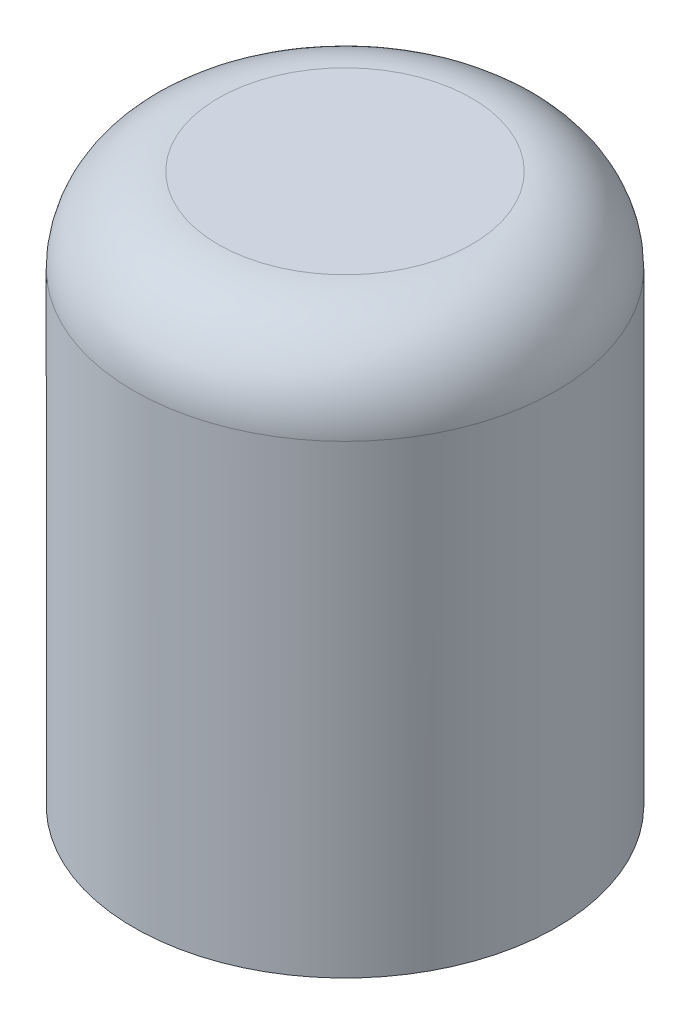
SolidWorks part; units mm, degrees
ref_plane "Front Plane" through (0, 0, 0) normal (0, 0, 1) x (1, 0, 0)
ref_plane "Top Plane" through (0, 0, 0) normal (0, 1, 0) x (1, 0, 0)
ref_plane "Right Plane" through (0, 0, 0) normal (1, 0, 0) x (0, 0, -1)
sketch "Sketch1" plane through (0, 0, 0) normal (0, 1, 0) x (1, 0, 0)
  circle A0 centre (0, 0) radius 5
  dimension "D1" = 10
extrude "Boss-Extrude1" add sketch "Sketch1" along normal blind 13
sketch "Insert" plane through (0, 0, 0) normal (0, -1, 0) x (1, 0, 0)
  line L0 (-1.6, 3) -> (-1.6, -3)
  line L1 (3.4, 0) -> (1.7771, 0) construction
  line L2 (-1.6, 0) -> (-0.8194, 0) construction
  arc A0 (-1.6, -3) -> (-1.6, 3) centre (0, 0) ccw
  dimension "D1" = 6
  dimension "D2" = 5
extrude "Cut-Extrude1" cut sketch "Insert" against normal blind 12.5
fillet "Fillet4" radius 2 2 edges at (3.4, 12.5, 0) (-1.6, 12.5, 0) type face fillet first side face at (-1.6, 6.25, 0) first side face at (0.9, 6.25, 0) second side face at (0.9, 12.5, 0)
fillet "Fillet5" radius 0.5 2 edges at (-1.6, 0, 0) (3.4, 0, 0) type face fillet first side face at (0.9, 0, 0) second side face at (0.9, 5.25, 0) second side face at (-1.6, 5.25, 0)
fillet "Fillet6" radius 2 1 edges at (0, 13, 5) type face fillet first side face at (0, 13, 5) second side face at (0, 13, 5)
